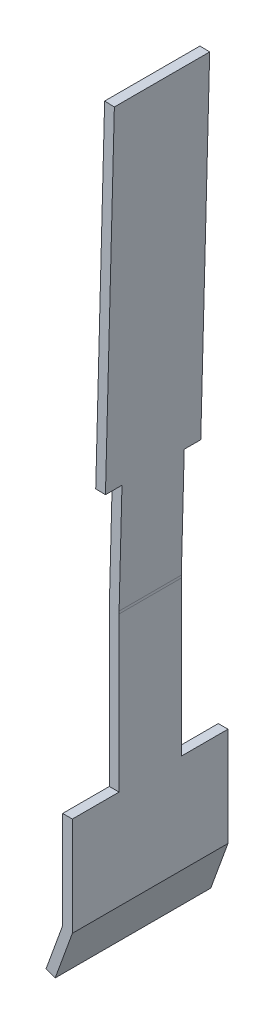
SolidWorks part; units mm, degrees
ref_plane "前视基准面" through (0, 0, 0) normal (0, 0, 1) x (1, 0, 0)
ref_plane "上视基准面" through (0, 0, 0) normal (0, 1, 0) x (1, 0, 0)
ref_plane "右视基准面" through (0, 0, 0) normal (1, 0, 0) x (0, 0, -1)
sketch "草图28" plane through (0, 0, 0) normal (0, 0, 1) x (1, 0, 0)
  line L0 (0, 0) -> (0, 18)
  line L1 (0, 18) -> (1.2172, 64.4841)
  dimension "D1" = 46.5
  dimension "D2" = 18
  dimension "D3" = 178.5
extrude "拉伸-薄壁2" add sketch "草图28" along normal blind 16 thin contours L0 L1 thin type one direction wall 1
sketch "草图31" plane through (0.5286, -0.0138, 0) normal (0.9997, -0.0262, 0) x (0, 0, -1)
  line L0 (-16, 64.4938) -> (-11.2, 64.4938)
  line L1 (-16, 64.4938) -> (0, 64.4938) construction
  line L2 (-11.2, 64.4938) -> (-11.2, 18.0069)
  line L3 (-16, 18.0069) -> (0, 18.0069) construction
  line L4 (-11.2, 18.0069) -> (-16, 18.0069)
  line L5 (-16, 18.0069) -> (-16, 64.4938)
  line L6 (-8, 64.4938) -> (-8, 18.0069) construction
  line L7 (0, 18.0069) -> (0, 64.4938) construction
  line L8 (-4.8, 18.0069) -> (0, 18.0069)
  line L9 (0, 18.0069) -> (0, 64.4938)
  line L10 (0, 64.4938) -> (-4.8, 64.4938)
  line L11 (-4.8, 64.4938) -> (-4.8, 18.0069)
  dimension "D1" = 4.8
  dimension "D2" = 8
extrude "切除-拉伸6" cut sketch "草图31" against normal through all
sketch "草图32" plane through (1, 0, 0) normal (1, 0, 0) x (0, 0, -1)
  line L0 (-8, 17.9869) -> (-8, 0) construction
  line L1 (-11.2, 17.9869) -> (-4.8, 17.9869) construction
  line L2 (-16, 0) -> (0, 0) construction
  line L4 (-16, 17.9869) -> (-11.2, 17.9869)
  line L5 (-11.2, 17.9869) -> (-11.2, 3.6785)
  line L6 (-11.2, 3.6785) -> (-16, 3.6785)
  line L7 (-16, 0) -> (-16, 17.9869) construction
  line L8 (-16, 3.6785) -> (-16, 17.9869)
  line L9 (-4.8, 3.6785) -> (0, 3.6785)
  line L10 (0, 3.6785) -> (0, 17.9869)
  line L11 (0, 17.9869) -> (-4.8, 17.9869)
  line L12 (-4.8, 17.9869) -> (-4.8, 3.6785)
extrude "切除-拉伸7" cut sketch "草图32" against normal blind 16
fillet "圆角1" radius 10 1 edges at (0, 18, 8) type face fillet first side face at (0.3045, 29.6276, 8) second side face at (0, 10.2218, 8)
fillet "圆角2" radius 10 1 edges at (1, 17.9869, 8) type face fillet first side face at (1.6084, 41.2224, 8) second side face at (1, 6.336, 8)
sketch "草图39" plane through (-0.471, 0.0123, 0) normal (-0.9997, 0.0262, 0) x (0, 0, 1)
  line L0 (11.2, 64.4938) -> (12.9, 64.4938)
  line L1 (12.9, 64.4938) -> (12.9, 29.4938)
  line L2 (12.9, 29.4938) -> (11.2, 29.4938)
  line L3 (11.2, 64.4938) -> (11.2, 18.1247) construction
  line L4 (8, 64.4938) -> (8, 31.8559) construction
  line L5 (11.2, 64.4938) -> (4.8, 64.4938) construction
  line L6 (11.2, 64.4938) -> (11.2, 29.4938)
  line L7 (4.8, 64.4938) -> (3.1, 64.4938)
  line L8 (3.1, 64.4938) -> (3.1, 29.4938)
  line L9 (3.1, 29.4938) -> (4.8, 29.4938)
  line L10 (4.8, 64.4938) -> (4.8, 29.4938)
  dimension "D1" = 1.7
  dimension "D2" = 35
extrude "凸台-拉伸1" add sketch "草图39" against normal blind 1
sketch "草图40" plane through (0.4714, 18.0008, 0) normal (0.0262, 0.9997, 0) x (0.9997, -0.0262, 0)
  line L1 (-0.4712, -11.2) -> (0.5288, -11.2)
  line L2 (-0.4712, -11.2) -> (-0.4712, -16)
  line L3 (-0.4712, -16) -> (0.5288, -16)
  line L4 (0.5288, -11.2) -> (0.5288, -16)
extrude "切除-拉伸8" cut sketch "草图40" against normal blind 10
sketch "草图41" plane through (0.4714, 18.0008, 0) normal (0.0262, 0.9997, 0) x (0.9997, -0.0262, 0)
  line L6 (0.5288, -4.8) -> (0.5288, 0) construction
  line L7 (0.5288, -4.8) -> (-2.736, -4.8)
  line L8 (0.5288, -4.8) -> (0.5288, 1.6576)
  line L9 (0.5288, 1.6576) -> (-2.736, 1.6576)
  line L10 (-2.736, -4.8) -> (-2.736, 1.6576)
extrude "切除-拉伸9" cut sketch "草图41" against normal blind 10
sketch "草图42" plane through (1, 0, 0) normal (1, 0, 0) x (0, 0, -1)
  line L0 (0, 0) -> (0, 3.6785) construction
  line L1 (-8, 0) -> (-8, 5.3029) construction
  line L2 (-4.8, 3.6785) -> (0, 3.6785)
  line L3 (-4.8, 3.6785) -> (-4.8, 1.9985)
  line L4 (-4.8, 1.9985) -> (0, 1.9985)
  line L5 (0, 3.6785) -> (0, 1.9985)
  line L6 (-16, 0) -> (0, 0) construction
  line L7 (-16, 3.6785) -> (-16, 1.9985)
  line L8 (-11.2, 1.9985) -> (-16, 1.9985)
  line L9 (-11.2, 3.6785) -> (-11.2, 1.9985)
  line L10 (-11.2, 3.6785) -> (-16, 3.6785)
  dimension "D1" = 1.68
extrude "切除-拉伸10" cut sketch "草图42" against normal blind 10
sketch "草图43" plane through (0, 0, 0) normal (-1, 0, 0) x (0, 0, 1)
  line L1 (0, 0) -> (16, 0)
  line L2 (0, 0) -> (0, -8)
  line L3 (0, -8) -> (16, -8)
  line L4 (16, 0) -> (16, -8)
  dimension "D2" = 8
sketch "草图44" plane through (0, 0, 0) normal (0, 0, -1) x (-1, 0, 0)
  line L0 (0, 0) -> (0, -8)
  line L1 (0, -8) -> (1.7101, -12.6985)
  dimension "D1" = 8
  dimension "D2" = 5
  dimension "D3" = 160
extrude "拉伸-薄壁3" add sketch "草图44" against normal blind 16 thin thin type one direction wall 1
